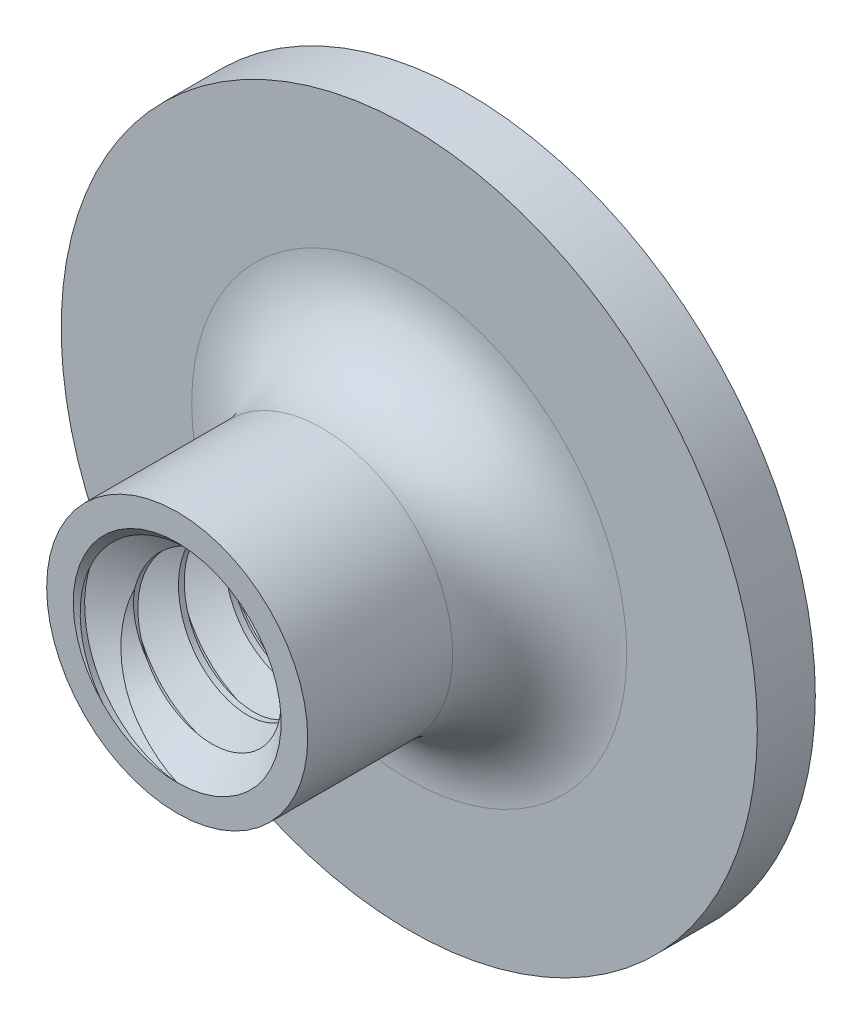
SolidWorks part; units mm, degrees
ref_plane "Front Plane" through (0, 0, 0) normal (0, 0, 1) x (1, 0, 0)
ref_plane "Top Plane" through (0, 0, 0) normal (0, 1, 0) x (1, 0, 0)
ref_plane "Right Plane" through (0, 0, 0) normal (1, 0, 0) x (0, 0, -1)
sketch "Sketch1" plane through (0, 0, 0) normal (0, 0, 1) x (1, 0, 0)
  circle A0 centre (0, 0) radius 4.7625
  circle A1 centre (0, 0) radius 1.4224
  dimension "D1" = 2.8448
extrude "Extrude1" add sketch "Sketch1" along normal blind 0.7937
sketch "Sketch2" plane through (0, 0, 0.7937) normal (0, 0, 1) x (1, 0, 0)
  circle A0 centre (0, 0) radius 1.7859
  circle A1 centre (0, 0) radius 1.4224
extrude "Extrude2" add sketch "Sketch2" along normal blind 3.175
sketch "Sketch3" plane through (0, 0, 0) normal (0, 0, -1) x (-1, 0, 0)
  circle A0 centre (0, 0) radius 1.4224 construction
  circle A1 centre (0, 0) radius 1.4224
curve "Helix/Spiral1" pitch 0.635 height 6.35 radius 1.4224 centre (0, 0, 0) axis (0, 0, 1) start towards (-1, 0, 0) parameters "pitch"=0.635
sketch "Sketch4" plane through (0, 0, 0) normal (0, 1, 0) x (1, 0, 0)
  line L0 (-1.4224, 0.5556) -> (-1.4224, 0)
  line L1 (-1.4224, 0) -> (-1.01, 0.2381)
  line L2 (-1.01, 0.2381) -> (-1.01, 0.3175)
  line L3 (-1.01, 0.3175) -> (-1.4224, 0.5556)
  line L4 (-1.01, 0.2778) -> (-1.4224, 0.2778) construction
  line L5 (-1.2162, 0.1191) -> (-1.2162, 0.4366) construction
  dimension "D2" = 0.3175
  dimension "D3" = 60
sweep "Sweep1" add profiles "Sketch4" path "Helix/Spiral1"
sketch "Sketch5" plane through (0, 0, 0) normal (0, 0, -1) x (-1, 0, 0)
  circle A1 centre (0, 0) radius 4.7625
  circle A2 centre (0, 0) radius 4.7625
  dimension "D1" = 0
extrude "Cut-Extrude1" cut sketch "Sketch5" along normal through all
sketch "Sketch6" plane through (0, 0, 0) normal (0, 0, -1) x (-1, 0, 0)
  circle A0 centre (0, 0) radius 1.4224 construction
  circle A1 centre (0, 0) radius 1.4224 construction
  circle A2 centre (0, 0) radius 1.4732
  dimension "D1" = 0.0508
extrude "Cut-Extrude2" cut sketch "Sketch6" against normal through all draft 45
sketch "Sketch7" plane through (0, 0, 3.9688) normal (0, 0, 1) x (1, 0, 0)
  circle A1 centre (0, 0) radius 1.7859
  circle A2 centre (0, 0) radius 1.7859
  dimension "D1" = 0
extrude "Cut-Extrude3" cut sketch "Sketch7" along normal through all
sketch "Sketch8" plane through (0, 0, 3.9688) normal (0, 0, 1) x (1, 0, 0)
  circle A0 centre (0, 0) radius 1.4224 construction
  circle A1 centre (0, 0) radius 1.4224
extrude "Cut-Extrude4" cut sketch "Sketch8" against normal through all draft 45
fillet "Fillet1" radius 1.1906 1 edges at (1.7859, 0, 0.7937)
equation "\"D1@Sketch1\" = \"OD@Sketch2\""
equation "\"D3@Helix/Spiral1\" = \"height@Extrude2\"+.125"
equation "\"D1@Sketch4\" = \"pitch@Helix/Spiral1\"*.125"
equation "\"D2@Sketch4\" = \"pitch@Helix/Spiral1\"*.5"
equation "\"D1@Fillet1\" = \"base thickness@Extrude1\"*1.50"
